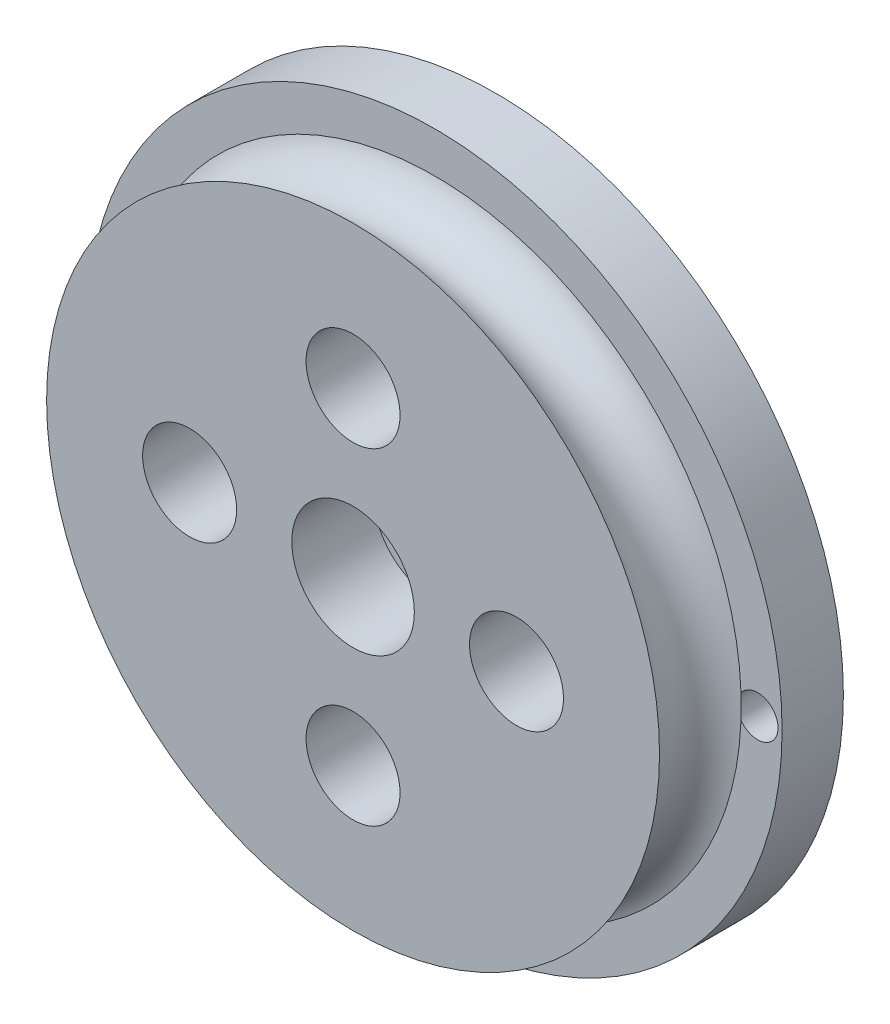
SolidWorks part; units mm, degrees
ref_plane "Front Plane" through (0, 0, 0) normal (0, 0, 1) x (1, 0, 0)
ref_plane "Top Plane" through (0, 0, 0) normal (0, 1, 0) x (1, 0, 0)
ref_plane "Right Plane" through (0, 0, 0) normal (1, 0, 0) x (0, 0, -1)
sketch "Sketch2" plane through (0, 0, 0) normal (0, 0, 1) x (1, 0, 0)
  circle A0 centre (0, 0) radius 15
  circle A1 centre (0, 0) radius 3
  circle A2 centre (-8, 0) radius 2.3
  circle A3 centre (0, 8) radius 2.3
  circle A4 centre (8, 0) radius 2.3
  circle A5 centre (0, -8) radius 2.3
  point P11 (0, 0)
  dimension "D1" = 4.6
  dimension "D2" = 6
  dimension "D3" = 30
  dimension "D4" = 8
extrude "Boss-Extrude1" add sketch "Sketch2" along normal blind 4
sketch "Sketch3" plane through (0, 0, 0) normal (0, 0, 1) x (1, 0, 0)
  line L0 (0, 18.407) -> (0, -24.0857) construction
  circle A0 centre (0, 0) radius 17
  circle A1 centre (0, 0) radius 1.475
  circle A2 centre (-15.8, 0) radius 1
  circle A3 centre (15.8, 0) radius 1
  dimension "D1" = 2
  dimension "D3" = 34
  dimension "D2" = 15.8
extrude "Boss-Extrude2" add sketch "Sketch3" against normal blind 3
sketch "Sketch4" plane through (0, 0, -3) normal (0, 0, -1) x (-1, 0, 0)
  circle A0 centre (0, 0) radius 1.475
  circle A1 centre (0, 0) radius 10
  dimension "D1" = 20
extrude "Boss-Extrude3" [suppressed] add sketch "Sketch4" along normal blind 3.5
sketch "Sketch5" [suppressed] plane through (0, 0, -6.5) normal (0, 0, -1) x (-1, 0, 0)
  line L0 (0, 18.407) -> (0, -24.0857) construction
  circle A0 centre (0, 0) radius 16
  circle A1 centre (0, 0) radius 1.475
  circle A2 centre (-13.2, 0) radius 1
  circle A3 centre (13.2, 0) radius 1
  dimension "D1" = 2
  dimension "D2" = 13.2
extrude "Boss-Extrude4" [suppressed] add sketch "Sketch5" along normal blind 3
sketch "Sketch6" plane through (0, 0, 4) normal (0, 0, 1) x (1, 0, 0)
  circle A0 centre (0, 0) radius 16
  circle A1 centre (0, 0) radius 12.5
  dimension "D1" = 32
  dimension "D2" = 25
sketch "Sketch7" plane through (0, 0, 0) normal (1, 0, 0) x (0, 0, -1)
  line L0 (0, 0) -> (-4, 0) construction
  line L1 (0, 17) -> (0, -17) construction
  line L2 (-4, 16) -> (-4, -16) construction
  line L3 (-4, 15) -> (0, 15)
  arc A0 (-4, 15) -> (0, 15) centre (-2, 15.5906) ccw
revolve "Cut-Revolve1" cut sketch "Sketch7" angle 360 about L0
